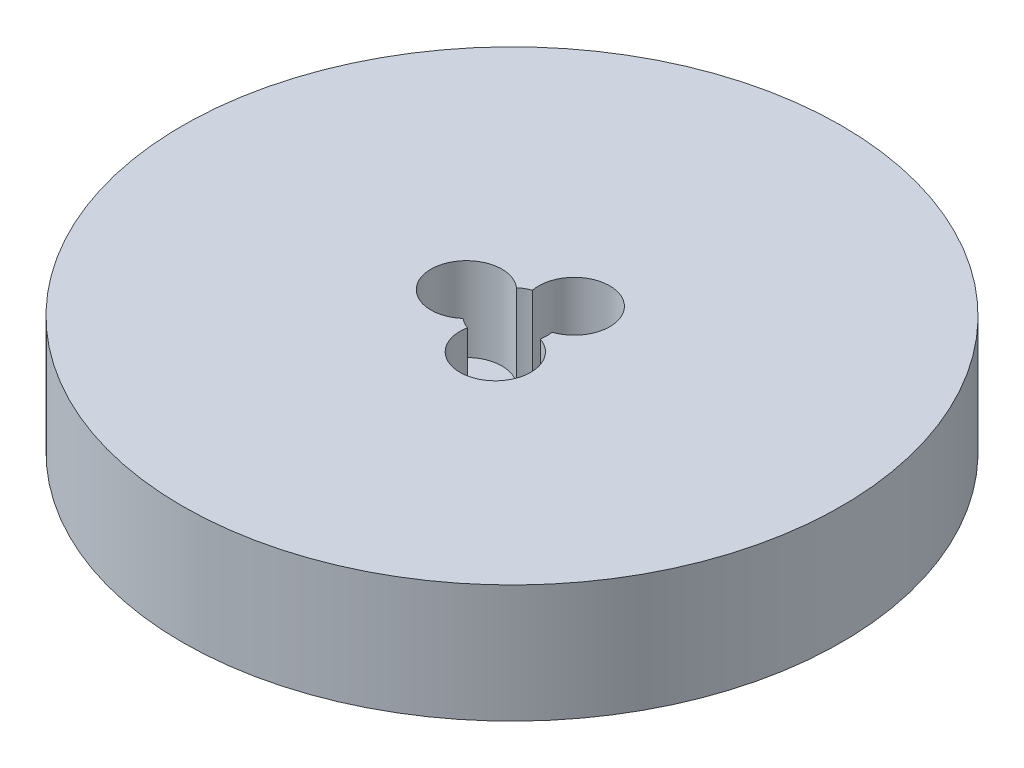
SolidWorks part; units mm, degrees
ref_plane "Front Plane" through (0, 0, 0) normal (0, 0, 1) x (1, 0, 0)
ref_plane "Top Plane" through (0, 0, 0) normal (0, 1, 0) x (1, 0, 0)
ref_plane "Right Plane" through (0, 0, 0) normal (1, 0, 0) x (0, 0, -1)
sketch "Sketch1" plane through (0, 0, 0) normal (0, 1, 0) x (1, 0, 0)
  circle A0 centre (0, 0) radius 47.5
  dimension "FLANGE_OD" = 95
extrude "Boss-Extrude1" add sketch "Sketch1" along normal blind 17
sketch "Sketch2" plane through (0, 0, 0) normal (0, 1, 0) x (1, 0, 0)
  circle A0 centre (0, 0) radius 5
  dimension "BORE_D" = 10
extrude "Cut-Extrude1" cut sketch "Sketch2" along normal through all
sketch "Sketch3" plane through (0, 17, 0) normal (0, 1, 0) x (1, 0, 0)
  circle A0 centre (0, 0) radius 6.5693 construction
  circle A1 centre (-6.5693, 0) radius 5.114
  dimension "BOLT_D" = 10.2279
  dimension "BOLT_PCD" = 13.1386
extrude "Cut-Extrude2" cut sketch "Sketch3" against normal blind 12.0927
pattern_circular "CirPattern1" count 3 over 360 about axis through (0, 0, 0) along (0, 1, 0) of "Cut-Extrude2"
